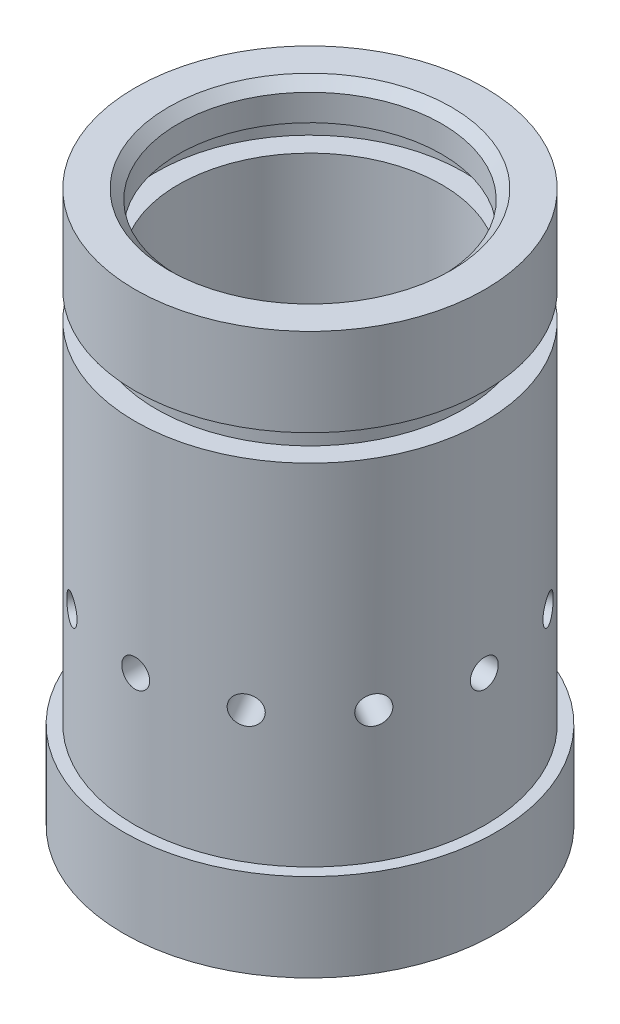
SolidWorks part; units mm, degrees
material "6061 Alloy"
ref_plane "Front Plane" through (0, 0, 0) normal (0, 0, 1) x (1, 0, 0)
ref_plane "Top Plane" through (0, 0, 0) normal (0, 1, 0) x (1, 0, 0)
ref_plane "Right Plane" through (0, 0, 0) normal (1, 0, 0) x (0, 0, -1)
sketch "Sketch1" plane through (0, 0, 0) normal (0, 0, 1) x (1, 0, 0)
  line L0 (0, 0) -> (0, 10.9165) construction
  line L1 (19.05, -57.6721) -> (19.05, -16.0161)
  line L2 (19.05, -16.0161) -> (20.447, -14.6191)
  line L3 (20.447, -14.6191) -> (25.2857, -14.6191)
  line L6 (25.2857, -14.6191) -> (25.2857, -57.6721)
  line L7 (25.2857, -57.6721) -> (19.05, -57.6721)
  line L8 (19.05, -57.6721) -> (15.875, -57.6721)
  line L9 (15.875, -57.6721) -> (25.7175, -94.4048)
  line L11 (25.7175, -94.4048) -> (26.9875, -94.4048)
  line L13 (15.875, -57.6721) -> (7.9375, -28.0489) construction
  line L14 (26.9875, -81.7048) -> (26.9875, -94.4048)
  line L15 (25.2857, -57.6721) -> (25.2857, -81.7048)
  line L16 (-26.9875, -81.7048) -> (26.9875, -81.7048) construction
  line L17 (25.2857, -81.7048) -> (26.9875, -81.7048)
  line L18 (-26.9875, -81.7048) -> (-26.9875, -94.4048)
  line L19 (-26.9875, -94.4048) -> (26.9875, -94.4048) construction
  line L20 (-22.2123, -14.6191) -> (22.2123, -14.6191) construction
  line L21 (19.05, -19.8261) -> (22.225, -19.8261)
  line L22 (25.2857, -27.3191) -> (22.225, -27.3191)
  line L23 (25.2857, -27.3191) -> (25.2857, -31.1291)
  line L24 (25.2857, -31.1291) -> (22.225, -31.1291)
  line L25 (22.225, -27.3191) -> (22.225, -31.1291)
  line L26 (19.05, -19.8261) -> (19.05, -23.6361)
  line L27 (19.05, -23.6361) -> (22.225, -23.6361)
  line L28 (22.225, -19.8261) -> (22.225, -23.6361)
  line L29 (-25.7175, -94.4048) -> (-26.9875, -94.4048)
  line L30 (-15.875, -57.6721) -> (-25.7175, -94.4048)
  line L31 (-22.225, -19.8261) -> (-22.225, -23.6361)
  line L32 (-19.05, -23.6361) -> (-22.225, -23.6361)
  line L33 (-19.05, -19.8261) -> (-19.05, -23.6361)
  line L34 (-22.225, -27.3191) -> (-22.225, -31.1291)
  line L35 (-25.2857, -31.1291) -> (-22.225, -31.1291)
  line L36 (-25.2857, -27.3191) -> (-25.2857, -31.1291)
  line L37 (-25.2857, -27.3191) -> (-22.225, -27.3191)
  line L38 (-19.05, -19.8261) -> (-22.225, -19.8261)
  line L39 (-25.2857, -81.7048) -> (-26.9875, -81.7048)
  line L40 (-25.2857, -57.6721) -> (-25.2857, -81.7048)
  line L41 (-19.05, -57.6721) -> (-15.875, -57.6721)
  line L42 (-25.2857, -57.6721) -> (-19.05, -57.6721)
  line L43 (-25.2857, -14.6191) -> (-25.2857, -57.6721)
  line L44 (-20.447, -14.6191) -> (-25.2857, -14.6191)
  line L45 (-19.05, -16.0161) -> (-20.447, -14.6191)
  line L46 (-19.05, -57.6721) -> (-19.05, -16.0161)
  point P26 (25.2857, -14.6191)
  point P37 (15.875, -57.6721)
  point P53 (-15.875, -57.6721)
  point P54 (-25.2857, -14.6191)
  dimension "D1" = 44.45
  dimension "D2" = 12.7
  dimension "D3" = 44.45
  dimension "D4" = 3.81
  dimension "D5" = 19.05
  dimension "D6" = 45
  dimension "D7" = 1.397
  dimension "D8" = 3.0607
  dimension "D9" = 3.81
revolve "Revolve1" add sketch "Sketch1" angle 360 about L0 region at (22.1785, -37.2764, 0) region at (22.6048, -71.4974, 0)
ref_plane "Plane1" through (0, 0, -25.2857) normal (0, 0, -1) x (-1, 0, 0)
sketch "Sketch2" plane through (0, 0, -25.2857) normal (0, 0, -1) x (-1, 0, 0)
  point P0 (0, -62.6548)
  point P2 (0, -61.3848)
hole_wizard "#10-32 Tapped Hole1" positions "Sketch2" profile "Sketch3" tap size "#10-32" standard "ANSI Inch"
sketch "Sketch3" plane through (0, -62.6548, -25.2857) normal (1, 0, 0) x (0, 1, 0)
  line L0 (0, 0) -> (0, 7.5633)
  line L1 (0, 7.5633) -> (2.0193, 6.35)
  line L2 (2.0193, 6.35) -> (2.0193, 0)
  line L5 (2.0193, 0) -> (0, 0)
  line L10 (0, 7.5633) -> (-2.0193, 6.35) construction
  line L11 (0, -6.35) -> (0, 107.95) construction
  dimension "Tap Drill Dia." = 4.0386
  dimension "Tap Drill Depth" = 6.35
  dimension "Drill Angle" = 118
pattern_circular "CirPattern1" count 12 over 360 about axis through (0, 0, 0) along (0, -1, 0) of "#10-32 Tapped Hole1" reverse direction yes
